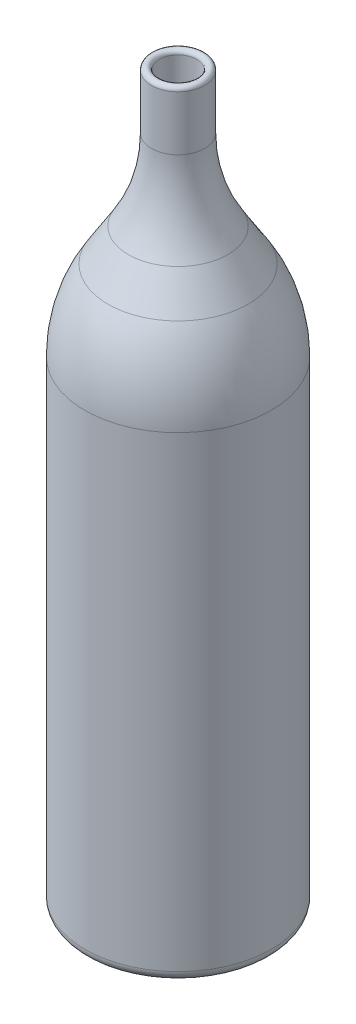
SolidWorks part; units mm, degrees
ref_plane "Front Plane" through (0, 0, 0) normal (0, 0, 1) x (1, 0, 0)
ref_plane "Top Plane" through (0, 0, 0) normal (0, 1, 0) x (1, 0, 0)
ref_plane "Right Plane" through (0, 0, 0) normal (1, 0, 0) x (0, 0, -1)
sketch "Sketch2" plane through (0, 0, 0) normal (0, 0, 1) x (1, 0, 0)
  line L0 (0, 0) -> (0, 274) construction
  line L1 (0, 274) -> (-10, 274)
  line L2 (-10, 274) -> (-10, 252)
  line L3 (-18.6613, 221.7946) -> (-26.3387, 209.5081)
  line L4 (-35, 179.3027) -> (-35, 4)
  line L5 (-31, 0) -> (-29, 0)
  line L6 (-22.6253, 1.6703) -> (-4.6585, 11.7794)
  line L7 (0, 274) -> (0, 13)
  arc A0 (-26.3387, 209.5081) -> (-35, 179.3027) centre (22, 179.3027) ccw
  arc A1 (-10, 252) -> (-18.6613, 221.7946) centre (-67, 252) cw
  arc A2 (-35, 4) -> (-31, 0) centre (-31, 4) ccw
  arc A3 (-29, 0) -> (-22.6253, 1.6703) centre (-29, 13) ccw
  arc A4 (-4.6585, 11.7794) -> (0, 13) centre (0, 3.5) cw
  point P19 (0, 0)
  point P20 (0, 0)
  dimension "D6" = 57
  dimension "D4" = 4
  dimension "D8" = 13
  dimension "D11" = 3.5
  dimension "D10" = 9.5
  dimension "D1" = 274
  dimension "D2" = 10
  dimension "D3" = 35
  dimension "D5" = 148
  dimension "D7" = 22
  dimension "D9" = 6
revolve "Revolve1" add sketch "Sketch2" angle 360 about L0
shell "Shell1" thickness 3 removed face at (0, 274, -10)
fillet "Fillet1" 2 edges at (0, 274, -10) (0, 274, -7) type full round first side face at (0, 252, -10) second side face at (0, 252, -7) middle face at (0, 274, -7)
